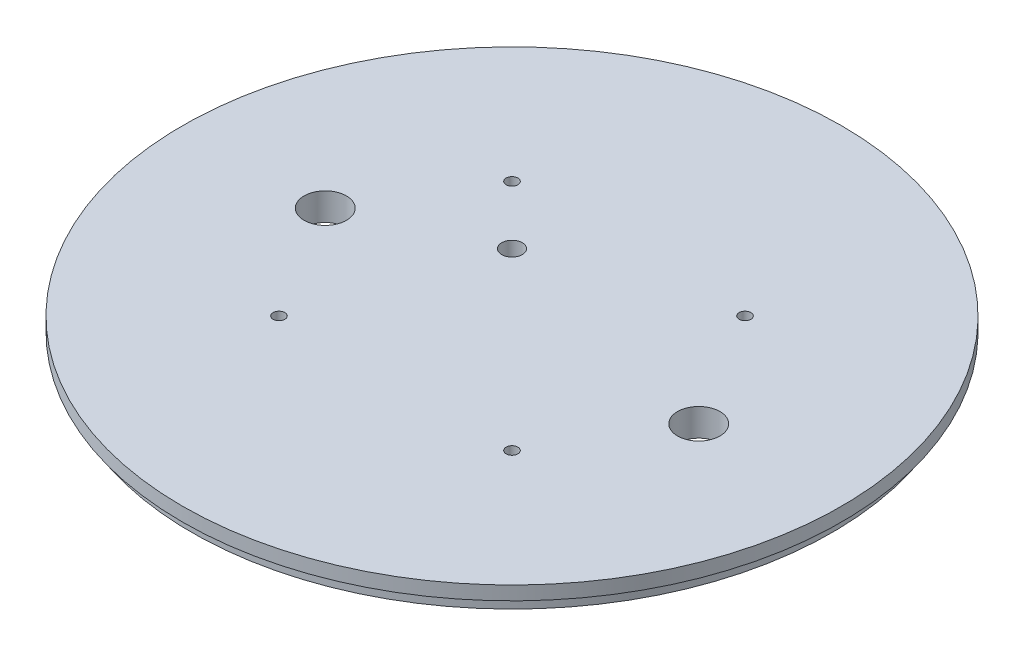
SolidWorks part; units mm, degrees
material "6061-T6 (SS)"
ref_plane "Front Plane" through (0, 0, 0) normal (0, 0, 1) x (1, 0, 0)
ref_plane "Top Plane" through (0, 0, 0) normal (0, 1, 0) x (1, 0, 0)
ref_plane "Right Plane" through (0, 0, 0) normal (1, 0, 0) x (0, 0, -1)
sketch "Sketch1" plane through (0, 0, 0) normal (0, 1, 0) x (1, 0, 0)
  line L0 (0, -76.2) -> (0, 76.2) construction
  line L1 (-76.2, 0) -> (76.2, 0) construction
  line L2 (-26.9408, 26.9408) -> (0, 0) construction
  line L3 (0, 56.7387) -> (0, 29.6936) construction
  line L4 (3.6407, 56.7387) -> (3.6407, 29.6936) construction
  line L5 (-3.6407, 56.7387) -> (-3.6407, 29.6936) construction
  line L6 (0, -56.7387) -> (0, -29.6936) construction
  line L7 (3.6407, -56.7387) -> (3.6407, -29.6936) construction
  line L8 (-3.6407, -56.7387) -> (-3.6407, -29.6936) construction
  line L9 (-53.8815, -53.8815) -> (54.3236, 54.3236) construction
  circle A0 centre (0, 0) radius 76.2
  circle A1 centre (0, 0) radius 3.175 construction
  circle A2 centre (43.18, 0) radius 4.9022
  circle A3 centre (-43.18, 0) radius 4.9022
  circle A4 centre (-26.9408, 26.9408) radius 1.3589
  arc A6 (3.6407, 56.7387) -> (-3.6407, 56.7387) centre (0, 56.7387) ccw construction
  arc A7 (-3.6407, 29.6936) -> (3.6407, 29.6936) centre (0, 29.6936) ccw construction
  arc A8 (3.6407, -56.7387) -> (-3.6407, -56.7387) centre (0, -56.7387) cw construction
  arc A9 (-3.6407, -29.6936) -> (3.6407, -29.6936) centre (0, -29.6936) cw construction
  circle A10 centre (26.9408, -26.9408) radius 1.3589
  circle A11 centre (-13.4704, 13.4704) radius 2.3813
  circle A12 centre (-26.9408, -26.9408) radius 1.3589
  circle A13 centre (26.9408, 26.9408) radius 1.3589
  circle A14 centre (-26.9408, 26.9408) radius 1.3589
  circle A15 centre (26.9408, -26.9408) radius 1.3589
  circle A16 centre (26.9408, 26.9408) radius 1.3589
  circle A17 centre (-26.9408, -26.9408) radius 1.3589
  point P16 (0, 43.2162)
  point P19 (0, 0)
  point P26 (0, -43.2162)
  point P50 (0, 0)
  dimension "D1" = 152.4
  dimension "D2" = 6.35
  dimension "D3" = 9.8044
  dimension "D5" = 2.7178
  dimension "D8" = 4.7625
  dimension "D6" = 38.1
  dimension "D7" = 45
  dimension "D4" = 45
  dimension "D9" = 43.18
  dimension "D10" = 4
extrude "Boss-Extrude1" add sketch "Sketch1" along normal blind 6.35 contours A0 A13 A10 A4 A2 A3 A11 A12 region at (0.0133, 0, 0.0133)
sketch "Sketch2" plane through (0, 0, 0) normal (0, -1, 0) x (1, 0, 0)
  circle A0 centre (0, 0) radius 76.2
  circle A1 centre (0, 0) radius 74.041
  dimension "D1" = 152.4
  dimension "D2" = 148.082
extrude "Cut-Extrude1" cut sketch "Sketch2" against normal blind 3.175
sketch "Sketch3" plane through (0, 6.35, 0) normal (0, 1, 0) x (1, 0, 0)
  line L0 (0, 76.2) -> (0, -76.2) construction
  line L1 (-76.2, 0) -> (76.2, 0) construction
  line L2 (0, 34.798) -> (0, 13.97) construction
  line L3 (3.2385, 34.798) -> (3.2385, 13.97)
  line L4 (-3.2385, 34.798) -> (-3.2385, 13.97)
  line L5 (0, -34.798) -> (0, -13.97) construction
  line L6 (3.2385, -34.798) -> (3.2385, -13.97)
  line L7 (-3.2385, -34.798) -> (-3.2385, -13.97)
  circle A0 centre (0, 0) radius 76.2 construction
  arc A1 (3.2385, 34.798) -> (-3.2385, 34.798) centre (0, 34.798) ccw
  arc A2 (-3.2385, 13.97) -> (3.2385, 13.97) centre (0, 13.97) ccw
  arc A3 (3.2385, -34.798) -> (-3.2385, -34.798) centre (0, -34.798) cw
  arc A4 (-3.2385, -13.97) -> (3.2385, -13.97) centre (0, -13.97) cw
  point P7 (0, 13.97)
  point P8 (0, 34.798)
  point P12 (0, 24.384)
  point P20 (0, -24.384)
  point P25 (0, -34.798)
  point P26 (0, -13.97)
  dimension "D1" = 13.97
  dimension "D2" = 20.828
  dimension "D3" = 6.477
extrude "Cut-Extrude2" cut sketch "Sketch3" against normal blind 3.556 from offset 3.175 offset against normal yes
equation "\"leadDist\"=1.5"
equation "\"Lead_Screw_Dist\" = 3.4in"
equation "\"Lead_Screw_Diam\" = 0.386in"
equation "\"D3@Sketch1\"=\"Lead_Screw_Diam\""
equation "\"D9@Sketch1\"=\"Lead_Screw_Dist\"/2"
